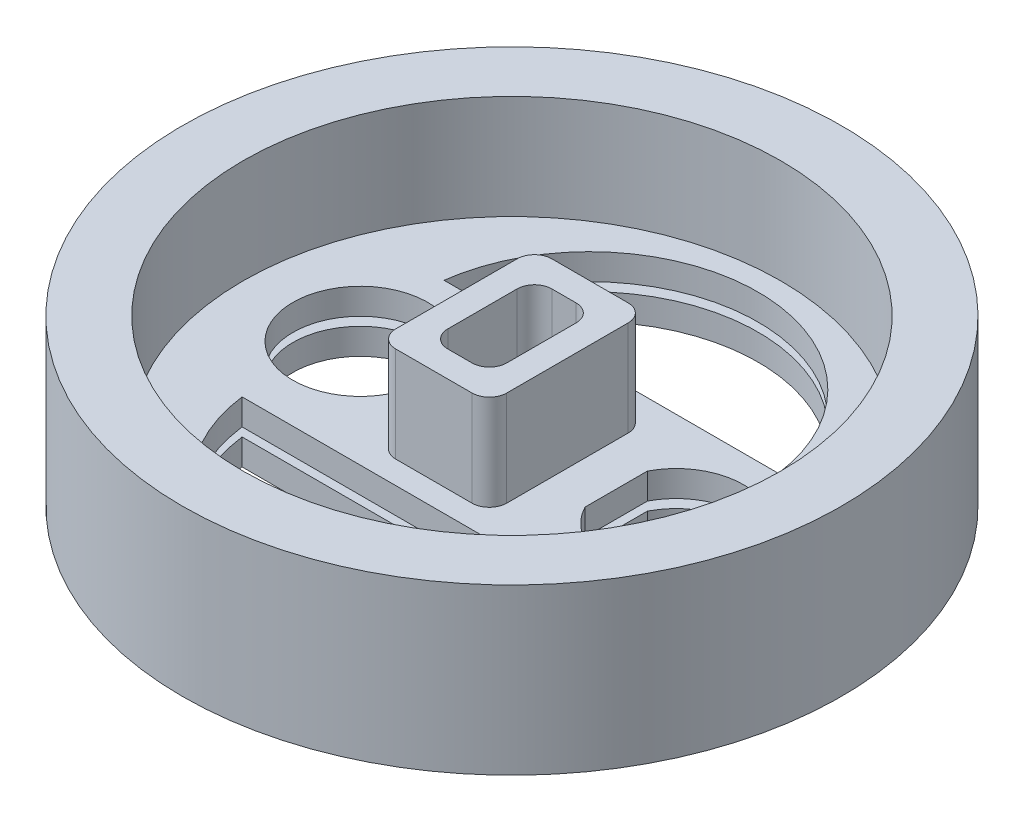
SolidWorks part; units mm, degrees
ref_plane "Front Plane" through (0, 0, 0) normal (0, 0, 1) x (1, 0, 0)
ref_plane "Top Plane" through (0, 0, 0) normal (0, 1, 0) x (1, 0, 0)
ref_plane "Right Plane" through (0, 0, 0) normal (1, 0, 0) x (0, 0, -1)
sketch "Sketch4" plane through (0, 0, 0) normal (0, 1, 0) x (1, 0, 0)
  line L0 (0, -46.7905) -> (24.3942, -46.7905) construction
  line L1 (0, -46.7905) -> (0, -24.9936) construction
  circle A0 centre (0, -46.7905) radius 17
  dimension "D1" = 34
extrude "Boss-Extrude3" add sketch "Sketch4" along normal blind 6 separate body
shell "Shell4" thickness 0.5 removed face at (0, 6, 63.7905) outward yes
ref_plane "Plane2" through (0, 0, 0) normal (0, 1, 0) x (1, 0, 0)
sketch "Sketch5" plane through (0, 0, 0) normal (0, 1, 0) x (1, 0, 0)
  line L0 (17, -46.7905) -> (-25.0436, -46.7905) construction
  line L1 (1.7, -43.7905) -> (-1.7, -43.7905)
  line L2 (1.7, -43.7905) -> (1.7, -49.7905)
  line L3 (1.7, -49.7905) -> (-1.7, -49.7905)
  line L4 (-1.7, -43.7905) -> (-1.7, -49.7905)
  line L5 (0, -29.7905) -> (0, -85.3723) construction
  circle A0 centre (0, -46.7905) radius 17 construction
  circle A1 centre (0, -46.7905) radius 17 construction
  dimension "D1" = 6
  dimension "D2" = 3.4
  dimension "D3" = 3
  dimension "D4" = 1.7
extrude "Boss-Extrude4" add sketch "Sketch5" along normal blind 7
shell "Shell5" thickness 1.5 removed face at (0, 7, 46.7905) outward yes
sketch "Sketch6" plane through (0, 0, 0) normal (0, 1, 0) x (1, 0, 0)
  line L1 (27.7675, -23.9741) -> (-27.2325, -23.9741)
  line L2 (27.7675, -23.9741) -> (27.7675, -67.9741)
  line L3 (27.7675, -67.9741) -> (-27.2325, -67.9741)
  line L4 (-27.2325, -23.9741) -> (-27.2325, -67.9741)
  dimension "D1" = 55
  dimension "D2" = 44
sketch "Sketch8" plane through (0, 1.5, 0) normal (0, 1, 0) x (1, 0, 0)
  line L0 (-9.7364, -40.9694) -> (9.5358, -40.9694)
  line L1 (3.2, -46.7905) -> (31.3222, -46.7905) construction
  line L2 (3.2, -51.2905) -> (3.2, -42.2905) construction
  line L3 (-9.7364, -52.6115) -> (9.5358, -52.6115)
  line L4 (-5.6513, -44.6283) -> (-5.6513, -48.2299)
  line L5 (0, -42.2905) -> (0, -27.4386) construction
  line L6 (3.2, -42.2905) -> (-3.2, -42.2905) construction
  line L7 (5.6513, -44.6283) -> (5.6513, -48.2299)
  arc A0 (-9.7364, -40.9694) -> (9.5358, -40.9694) centre (-0.1003, -42.217) cw
  arc A1 (-9.7364, -52.6115) -> (9.5358, -52.6115) centre (-0.1003, -51.3639) ccw
  arc A2 (-5.6513, -44.6283) -> (-5.6513, -48.2299) centre (-9.1002, -46.4291) ccw
  arc A3 (5.6513, -44.6283) -> (5.6513, -48.2299) centre (9.1002, -46.4291) cw
  point P21 (-9.7364, -40.9694)
extrude "Cut-Extrude2" cut sketch "Sketch8" against normal through all
fillet "Fillet1" radius 1 8 edges at (-1.7, 3.5, 49.7905) (1.7, 3.5, 49.7905) (-1.7, 3.5, 43.7905) (1.7, 3.5, 43.7905) (-3.2, 4.25, 42.2905) (3.2, 4.25, 42.2905) (3.2, 4.25, 51.2905) (-3.2, 4.25, 51.2905)
